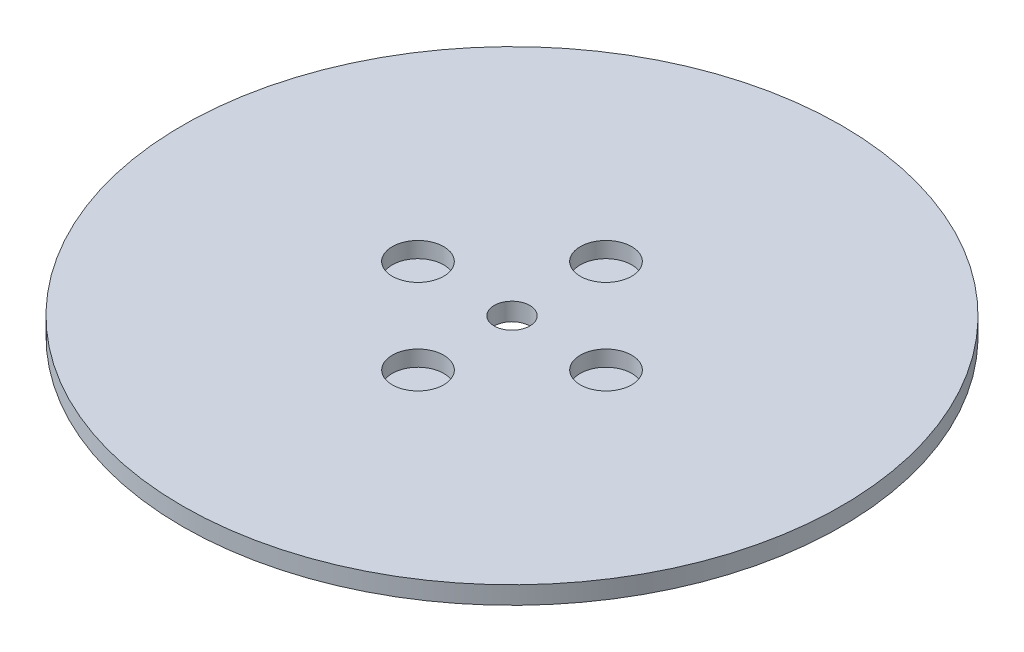
SolidWorks part; units mm, degrees
ref_plane "Front Plane" through (0, 0, 0) normal (0, 0, 1) x (1, 0, 0)
ref_plane "Top Plane" through (0, 0, 0) normal (0, 1, 0) x (1, 0, 0)
ref_plane "Right Plane" through (0, 0, 0) normal (1, 0, 0) x (0, 0, -1)
sketch "Sketch1" plane through (0, 0, 0) normal (0, 1, 0) x (1, 0, 0)
  circle A0 centre (0, 0) radius 92.5
  dimension "FLANGE_OD" = 185
extrude "Boss-Extrude1" add sketch "Sketch1" along normal blind 5
sketch "Sketch2" plane through (0, 0, 0) normal (0, 1, 0) x (1, 0, 0)
  circle A0 centre (0, 0) radius 5
  dimension "BORE_D" = 10
extrude "Cut-Extrude1" cut sketch "Sketch2" along normal through all
sketch "Sketch3" plane through (0, 5, 0) normal (0, 1, 0) x (1, 0, 0)
  circle A0 centre (0, 0) radius 26.3854 construction
  circle A1 centre (-26.3854, 0) radius 7.2189
  dimension "BOLT_D" = 14.4378
  dimension "BOLT_PCD" = 52.7708
extrude "Cut-Extrude2" cut sketch "Sketch3" against normal blind 4.4355
pattern_circular "CirPattern1" count 4 over 360 about axis through (0, 0, 0) along (0, 1, 0) of "Cut-Extrude2"
